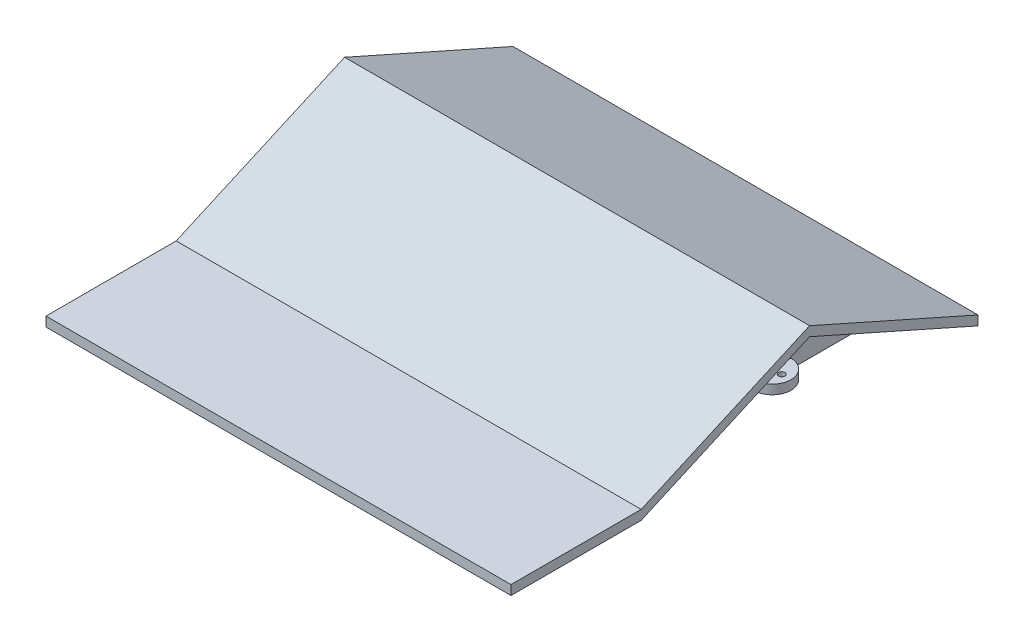
SolidWorks part; units mm, degrees
ref_plane "Front Plane" through (0, 0, 0) normal (0, 0, 1) x (1, 0, 0)
ref_plane "Top Plane" through (0, 0, 0) normal (0, 1, 0) x (1, 0, 0)
ref_plane "Right Plane" through (0, 0, 0) normal (1, 0, 0) x (0, 0, -1)
sketch "Sketch1" plane through (0, 0, 0) normal (1, 0, 0) x (0, 0, -1)
  line L0 (0, 0) -> (135, 0)
  line L1 (67.5, 0) -> (67.5, 30)
  line L2 (67.5, 30) -> (135, 0)
  line L3 (135, 0) -> (158.0421, -10.2409)
  line L4 (158.0421, -10.2409) -> (158.0421, -5.1205)
  line L5 (158.0421, -5.1205) -> (67.5, 35.1205)
  line L6 (67.5, 30) -> (0, 0)
  line L7 (0, 0) -> (-23.0421, -10.2409)
  line L8 (-23.0421, -10.2409) -> (-23.0421, -5.1205)
  line L9 (-23.0421, -5.1205) -> (67.5, 35.1205)
extrude "Boss-Extrude1" add sketch "Sketch1" against normal blind 250 contours L9 L8 L7 L6 L2 L3 L4 L5 region at (0, -3.4146, 12.2792)
sketch "Sketch2" plane through (0, 0, 0) normal (1, 0, 0) x (0, 0, -1)
  line L0 (0, 0) -> (135, 0)
  line L1 (67.5, 30) -> (158.0421, -10.2409) construction
  line L2 (135, 0) -> (67.5, 30)
  line L3 (67.5, 30) -> (0, 0)
extrude "Boss-Extrude2" add sketch "Sketch2" against normal blind 25
sketch "Sketch3" plane through (0, 0, 0) normal (1, 0, 0) x (0, 0, -1)
  line L0 (0, 0) -> (135, 0)
  line L1 (135, 0) -> (67.5, 30)
  line L2 (67.5, 30) -> (0, 0)
extrude "Cut-Extrude1" cut sketch "Sketch3" against normal blind 20
sketch "Sketch4" plane through (-250, 0, 0) normal (-1, 0, 0) x (0, 0, 1)
  line L0 (-135, 0) -> (0, 0)
  line L1 (0, 0) -> (-67.5, 30)
  line L2 (-67.5, 30) -> (-135, 0)
extrude "Boss-Extrude3" add sketch "Sketch4" against normal blind 25
sketch "Sketch5" plane through (-250, 0, 0) normal (-1, 0, 0) x (0, 0, 1)
  line L0 (-135, 0) -> (0, 0)
  line L1 (0, 0) -> (-67.5, 29.5827)
  line L2 (-67.5, 29.5827) -> (-135, 0)
extrude "Cut-Extrude2" cut sketch "Sketch5" against normal blind 20
sketch "Sketch6" plane through (0, 0, 0) normal (0, -1, 0) x (-1, 0, 0)
  line L0 (230, 67.5) -> (240, 67.5)
  circle A0 centre (230, 67.5) radius 10
  circle A1 centre (235, 67.5) radius 1.7
  line M1 (230, 0) -> (230, 135)
  line M3 (225, 135) -> (225, 0)
extrude "Boss-Extrude4" add sketch "Sketch6" against normal blind 5 contours A1 L0 A0 M1 | A1 L0 A0 M1 | A0 M3 | A0 M1 M3 region at (-234.1978, 0, -71.9602) region at (-234.1978, 0, -63.0398) region at (-227.5575, 0, -67.5) region at (-222.9498, 0, -67.5)
sketch "Sketch7" plane through (0, 0, 0) normal (0, -1, 0) x (-1, 0, 0)
  line L0 (20, 67.5) -> (10, 67.5)
  circle A0 centre (20, 67.5) radius 10
  circle A1 centre (15, 67.5) radius 1.7
  line M1 (20, 135) -> (20, 0)
  line M3 (25, 0) -> (25, 135)
extrude "Boss-Extrude5" add sketch "Sketch7" against normal blind 5 contours A1 L0 A0 M1 | A1 L0 A0 M1 | A0 M1 M3 | A0 M3 region at (-15.8022, 0, -63.0398) region at (-15.8022, 0, -71.9602) region at (-22.4425, 0, -67.5) region at (-27.0502, 0, -67.5)
sketch "Sketch8" plane through (-230, 0, 0) normal (-1, 0, 0) x (0, 0, 1)
  line L0 (-67.5, 5) -> (-67.5, 25)
  line L1 (-57.5, 5) -> (-77.5, 5) construction
  circle A0 centre (-67.5, 25) radius 1.5
extrude "Cut-Extrude3" cut sketch "Sketch8" against normal blind 10 contours A0 region at (-230, 23.9693, -66.4693)
sketch "Sketch9" plane through (-250, 0, 0) normal (-1, 0, 0) x (0, 0, 1)
  line L0 (23.0421, -5.1205) -> (93.0421, -5.1205)
  line L1 (93.0421, -5.1205) -> (93.0421, -10.2409)
  line L2 (93.0421, -10.2409) -> (23.0421, -10.2409)
  line L3 (23.0421, -10.2409) -> (23.0421, -5.1205)
extrude "Boss-Extrude7" add sketch "Sketch9" against normal blind 250
